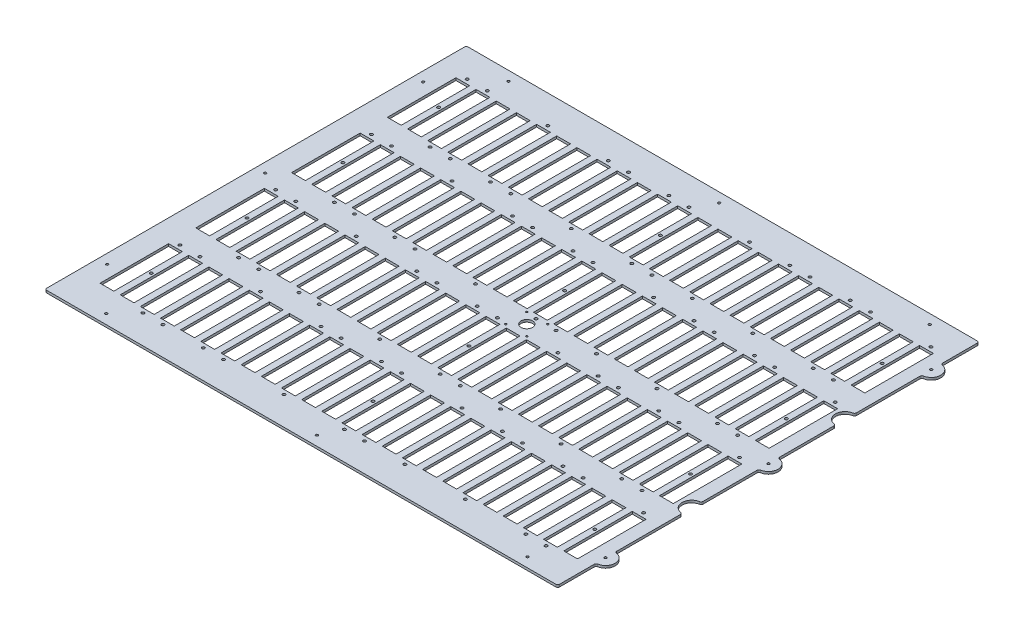
SolidWorks part; units mm, degrees
ref_plane "Front Plane" through (0, 0, 0) normal (0, 0, 1) x (1, 0, 0)
ref_plane "Top Plane" through (0, 0, 0) normal (0, 1, 0) x (1, 0, 0)
ref_plane "Right Plane" through (0, 0, 0) normal (1, 0, 0) x (0, 0, -1)
sketch "Sketch1" plane through (0, 0, 0) normal (0, 1, 0) x (1, 0, 0)
  line L0 (340.1822, 228.7524) -> (340.1822, 279.5524)
  line L1 (-340.1822, -279.5524) -> (340.1822, -279.5524)
  line L2 (-340.1822, -279.5524) -> (-340.1822, 279.5524)
  line L3 (-340.1822, 279.5524) -> (340.1822, 279.5524)
  line L4 (-340.1822, 0) -> (340.2584, 0) construction
  line L5 (-340.1822, -279.5524) -> (340.1822, 279.5524) construction
  line L6 (-340.1822, 279.5524) -> (340.1822, -279.5524) construction
  line L7 (340.1822, 114.4524) -> (340.1822, 203.3524)
  line L8 (340.1822, 12.6998) -> (340.1822, 89.0524)
  line L9 (340.1822, -279.5524) -> (340.1822, -228.7524)
  line L10 (340.1822, -89.0524) -> (340.1822, -12.6998)
  line L11 (340.1822, -203.3524) -> (340.1822, -114.4524)
  arc A0 (340.1822, 203.3524) -> (340.1822, 228.7524) centre (340.1822, 216.0524) ccw
  arc A1 (340.1822, -228.7524) -> (340.1822, -203.3524) centre (340.1822, -216.0524) ccw
  arc A2 (340.1822, -12.6998) -> (340.1822, 12.6998) centre (340.2584, 0) ccw
  arc A3 (340.1822, 114.4524) -> (340.1822, 89.0524) centre (340.1822, 101.7524) ccw
  arc A4 (340.1822, -89.0524) -> (340.1822, -114.4524) centre (340.1822, -101.7524) ccw
  point P0 (0, 0)
  dimension "D3" = 25.4
  dimension "D4" = 63.5
  dimension "D5" = 63.5
  dimension "D6" = 177.8
  dimension "D7" = 177.8
  dimension "D1" = 559.1048
  dimension "D2" = 680.3644
extrude "Boss-Extrude1" add sketch "Sketch1" along normal blind 3.175
sketch "Sketch17" plane through (0, 3.175, 0) normal (0, 1, 0) x (1, 0, 0)
  line L0 (340.1822, 279.5524) -> (-340.1822, 279.5524) construction
  line L1 (-314.7822, 254.1524) -> (327.4822, 254.1524) construction
  line L2 (-314.7822, 254.1524) -> (-314.7822, -254.1524) construction
  line L3 (-314.7822, -254.1524) -> (327.4822, -254.1524) construction
  line L4 (327.4822, 254.1524) -> (327.4822, -254.1524) construction
  line L5 (-340.1822, 279.5524) -> (-340.1822, -279.5524) construction
  line L6 (-340.1822, -279.5524) -> (340.1822, -279.5524) construction
  line L8 (-283.7677, 236.1184) -> (-265.4797, 236.1184)
  line L9 (-310.515, 236.1184) -> (-292.227, 236.1184)
  line L10 (-310.515, 236.1184) -> (-310.515, 145.1864)
  line L11 (-310.515, 145.1864) -> (-292.227, 145.1864)
  line L12 (-292.227, 236.1184) -> (-292.227, 145.1864)
  line L13 (-283.7677, 236.1184) -> (-283.7677, 145.1864)
  line L14 (-265.4797, 236.1184) -> (-265.4797, 145.1864)
  line L15 (-283.7677, 145.1864) -> (-265.4797, 145.1864)
  line L16 (-257.0204, 236.1184) -> (-238.7324, 236.1184)
  line L17 (-257.0204, 236.1184) -> (-257.0204, 145.1864)
  line L18 (-238.7324, 236.1184) -> (-238.7324, 145.1864)
  line L19 (-257.0204, 145.1864) -> (-238.7324, 145.1864)
  line L20 (-230.2731, 236.1184) -> (-211.9851, 236.1184)
  line L21 (-230.2731, 236.1184) -> (-230.2731, 145.1864)
  line L22 (-211.9851, 236.1184) -> (-211.9851, 145.1864)
  line L23 (-230.2731, 145.1864) -> (-211.9851, 145.1864)
  line L24 (-203.5258, 236.1184) -> (-185.2378, 236.1184)
  line L25 (-203.5258, 236.1184) -> (-203.5258, 145.1864)
  line L26 (-185.2378, 236.1184) -> (-185.2378, 145.1864)
  line L27 (-203.5258, 145.1864) -> (-185.2378, 145.1864)
  line L28 (-176.7785, 236.1184) -> (-158.4905, 236.1184)
  line L29 (-176.7785, 236.1184) -> (-176.7785, 145.1864)
  line L30 (-158.4905, 236.1184) -> (-158.4905, 145.1864)
  line L31 (-176.7785, 145.1864) -> (-158.4905, 145.1864)
  line L32 (-150.0312, 236.1184) -> (-131.7432, 236.1184)
  line L33 (-150.0312, 236.1184) -> (-150.0312, 145.1864)
  line L34 (-131.7432, 236.1184) -> (-131.7432, 145.1864)
  line L35 (-150.0312, 145.1864) -> (-131.7432, 145.1864)
  line L36 (-123.2839, 236.1184) -> (-104.9959, 236.1184)
  line L37 (-123.2839, 236.1184) -> (-123.2839, 145.1864)
  line L38 (-104.9959, 236.1184) -> (-104.9959, 145.1864)
  line L39 (-123.2839, 145.1864) -> (-104.9959, 145.1864)
  line L40 (-96.5366, 236.1184) -> (-78.2486, 236.1184)
  line L41 (-96.5366, 236.1184) -> (-96.5366, 145.1864)
  line L42 (-78.2486, 236.1184) -> (-78.2486, 145.1864)
  line L43 (-96.5366, 145.1864) -> (-78.2486, 145.1864)
  line L44 (-69.7893, 236.1184) -> (-51.5013, 236.1184)
  line L45 (-69.7893, 236.1184) -> (-69.7893, 145.1864)
  line L46 (-51.5013, 236.1184) -> (-51.5013, 145.1864)
  line L47 (-69.7893, 145.1864) -> (-51.5013, 145.1864)
  line L48 (-43.042, 236.1184) -> (-24.754, 236.1184)
  line L49 (-43.042, 236.1184) -> (-43.042, 145.1864)
  line L50 (-24.754, 236.1184) -> (-24.754, 145.1864)
  line L51 (-43.042, 145.1864) -> (-24.754, 145.1864)
  line L52 (-16.2947, 236.1184) -> (1.9933, 236.1184)
  line L53 (-16.2947, 236.1184) -> (-16.2947, 145.1864)
  line L54 (1.9933, 236.1184) -> (1.9933, 145.1864)
  line L55 (-16.2947, 145.1864) -> (1.9933, 145.1864)
  line L56 (10.4527, 236.1184) -> (28.7407, 236.1184)
  line L57 (10.4527, 236.1184) -> (10.4527, 145.1864)
  line L58 (28.7407, 236.1184) -> (28.7407, 145.1864)
  line L59 (10.4527, 145.1864) -> (28.7407, 145.1864)
  line L60 (37.2, 236.1184) -> (55.488, 236.1184)
  line L61 (37.2, 236.1184) -> (37.2, 145.1864)
  line L62 (55.488, 236.1184) -> (55.488, 145.1864)
  line L63 (37.2, 145.1864) -> (55.488, 145.1864)
  line L64 (63.9473, 236.1184) -> (82.2353, 236.1184)
  line L65 (63.9473, 236.1184) -> (63.9473, 145.1864)
  line L66 (82.2353, 236.1184) -> (82.2353, 145.1864)
  line L67 (63.9473, 145.1864) -> (82.2353, 145.1864)
  line L68 (90.6946, 236.1184) -> (108.9826, 236.1184)
  line L69 (90.6946, 236.1184) -> (90.6946, 145.1864)
  line L70 (108.9826, 236.1184) -> (108.9826, 145.1864)
  line L71 (90.6946, 145.1864) -> (108.9826, 145.1864)
  line L72 (117.4419, 236.1184) -> (135.7299, 236.1184)
  line L73 (117.4419, 236.1184) -> (117.4419, 145.1864)
  line L74 (135.7299, 236.1184) -> (135.7299, 145.1864)
  line L75 (117.4419, 145.1864) -> (135.7299, 145.1864)
  line L76 (144.1892, 236.1184) -> (162.4772, 236.1184)
  line L77 (144.1892, 236.1184) -> (144.1892, 145.1864)
  line L78 (162.4772, 236.1184) -> (162.4772, 145.1864)
  line L79 (144.1892, 145.1864) -> (162.4772, 145.1864)
  line L80 (170.9365, 236.1184) -> (189.2245, 236.1184)
  line L81 (170.9365, 236.1184) -> (170.9365, 145.1864)
  line L82 (189.2245, 236.1184) -> (189.2245, 145.1864)
  line L83 (170.9365, 145.1864) -> (189.2245, 145.1864)
  line L84 (197.6838, 236.1184) -> (215.9718, 236.1184)
  line L85 (197.6838, 236.1184) -> (197.6838, 145.1864)
  line L86 (215.9718, 236.1184) -> (215.9718, 145.1864)
  line L87 (197.6838, 145.1864) -> (215.9718, 145.1864)
  line L88 (224.4311, 236.1184) -> (242.7191, 236.1184)
  line L89 (224.4311, 236.1184) -> (224.4311, 145.1864)
  line L90 (242.7191, 236.1184) -> (242.7191, 145.1864)
  line L91 (224.4311, 145.1864) -> (242.7191, 145.1864)
  line L92 (251.1784, 236.1184) -> (269.4664, 236.1184)
  line L93 (251.1784, 236.1184) -> (251.1784, 145.1864)
  line L94 (269.4664, 236.1184) -> (269.4664, 145.1864)
  line L95 (251.1784, 145.1864) -> (269.4664, 145.1864)
  line L96 (277.9257, 236.1184) -> (296.2137, 236.1184)
  line L97 (277.9257, 236.1184) -> (277.9257, 145.1864)
  line L98 (296.2137, 236.1184) -> (296.2137, 145.1864)
  line L99 (277.9257, 145.1864) -> (296.2137, 145.1864)
  line L100 (304.673, 236.1184) -> (322.961, 236.1184)
  line L101 (304.673, 236.1184) -> (304.673, 145.1864)
  line L102 (322.961, 236.1184) -> (322.961, 145.1864)
  line L103 (304.673, 145.1864) -> (322.961, 145.1864)
  line L104 (-283.7677, 109.0422) -> (-265.4797, 109.0422)
  line L105 (-283.7677, 109.0422) -> (-283.7677, 18.1102)
  line L106 (-265.4797, 109.0422) -> (-265.4797, 18.1102)
  line L107 (-283.7677, 18.1102) -> (-265.4797, 18.1102)
  line L108 (-257.0204, 109.0422) -> (-238.7324, 109.0422)
  line L109 (-257.0204, 109.0422) -> (-257.0204, 18.1102)
  line L110 (-238.7324, 109.0422) -> (-238.7324, 18.1102)
  line L111 (-257.0204, 18.1102) -> (-238.7324, 18.1102)
  line L112 (-230.2731, 109.0422) -> (-211.9851, 109.0422)
  line L113 (-230.2731, 109.0422) -> (-230.2731, 18.1102)
  line L114 (-211.9851, 109.0422) -> (-211.9851, 18.1102)
  line L115 (-230.2731, 18.1102) -> (-211.9851, 18.1102)
  line L116 (-203.5258, 109.0422) -> (-185.2378, 109.0422)
  line L117 (-203.5258, 109.0422) -> (-203.5258, 18.1102)
  line L118 (-185.2378, 109.0422) -> (-185.2378, 18.1102)
  line L119 (-203.5258, 18.1102) -> (-185.2378, 18.1102)
  line L120 (-176.7785, 109.0422) -> (-158.4905, 109.0422)
  line L121 (-176.7785, 109.0422) -> (-176.7785, 18.1102)
  line L122 (-158.4905, 109.0422) -> (-158.4905, 18.1102)
  line L123 (-176.7785, 18.1102) -> (-158.4905, 18.1102)
  line L124 (-150.0312, 109.0422) -> (-131.7432, 109.0422)
  line L125 (-150.0312, 109.0422) -> (-150.0312, 18.1102)
  line L126 (-131.7432, 109.0422) -> (-131.7432, 18.1102)
  line L127 (-150.0312, 18.1102) -> (-131.7432, 18.1102)
  line L128 (-123.2839, 109.0422) -> (-104.9959, 109.0422)
  line L129 (-123.2839, 109.0422) -> (-123.2839, 18.1102)
  line L130 (-104.9959, 109.0422) -> (-104.9959, 18.1102)
  line L131 (-123.2839, 18.1102) -> (-104.9959, 18.1102)
  line L132 (-96.5366, 109.0422) -> (-78.2486, 109.0422)
  line L133 (-96.5366, 109.0422) -> (-96.5366, 18.1102)
  line L134 (-78.2486, 109.0422) -> (-78.2486, 18.1102)
  line L135 (-96.5366, 18.1102) -> (-78.2486, 18.1102)
  line L136 (-69.7893, 109.0422) -> (-51.5013, 109.0422)
  line L137 (-69.7893, 109.0422) -> (-69.7893, 18.1102)
  line L138 (-51.5013, 109.0422) -> (-51.5013, 18.1102)
  line L139 (-69.7893, 18.1102) -> (-51.5013, 18.1102)
  line L140 (-43.042, 109.0422) -> (-24.754, 109.0422)
  line L141 (-43.042, 109.0422) -> (-43.042, 18.1102)
  line L142 (-24.754, 109.0422) -> (-24.754, 18.1102)
  line L143 (-43.042, 18.1102) -> (-24.754, 18.1102)
  line L144 (-16.2947, 109.0422) -> (1.9933, 109.0422)
  line L145 (-16.2947, 109.0422) -> (-16.2947, 18.1102)
  line L146 (1.9933, 109.0422) -> (1.9933, 18.1102)
  line L147 (-16.2947, 18.1102) -> (1.9933, 18.1102)
  line L148 (10.4527, 109.0422) -> (28.7407, 109.0422)
  line L149 (10.4527, 109.0422) -> (10.4527, 18.1102)
  line L150 (28.7407, 109.0422) -> (28.7407, 18.1102)
  line L151 (10.4527, 18.1102) -> (28.7407, 18.1102)
  line L152 (37.2, 109.0422) -> (55.488, 109.0422)
  line L153 (37.2, 109.0422) -> (37.2, 18.1102)
  line L154 (55.488, 109.0422) -> (55.488, 18.1102)
  line L155 (37.2, 18.1102) -> (55.488, 18.1102)
  line L156 (63.9473, 109.0422) -> (82.2353, 109.0422)
  line L157 (63.9473, 109.0422) -> (63.9473, 18.1102)
  line L158 (82.2353, 109.0422) -> (82.2353, 18.1102)
  line L159 (63.9473, 18.1102) -> (82.2353, 18.1102)
  line L160 (90.6946, 109.0422) -> (108.9826, 109.0422)
  line L161 (90.6946, 109.0422) -> (90.6946, 18.1102)
  line L162 (108.9826, 109.0422) -> (108.9826, 18.1102)
  line L163 (90.6946, 18.1102) -> (108.9826, 18.1102)
  line L164 (117.4419, 109.0422) -> (135.7299, 109.0422)
  line L165 (117.4419, 109.0422) -> (117.4419, 18.1102)
  line L166 (135.7299, 109.0422) -> (135.7299, 18.1102)
  line L167 (117.4419, 18.1102) -> (135.7299, 18.1102)
  line L168 (144.1892, 109.0422) -> (162.4772, 109.0422)
  line L169 (144.1892, 109.0422) -> (144.1892, 18.1102)
  line L170 (162.4772, 109.0422) -> (162.4772, 18.1102)
  line L171 (144.1892, 18.1102) -> (162.4772, 18.1102)
  line L172 (170.9365, 109.0422) -> (189.2245, 109.0422)
  line L173 (170.9365, 109.0422) -> (170.9365, 18.1102)
  line L174 (189.2245, 109.0422) -> (189.2245, 18.1102)
  line L175 (170.9365, 18.1102) -> (189.2245, 18.1102)
  line L176 (197.6838, 109.0422) -> (215.9718, 109.0422)
  line L177 (197.6838, 109.0422) -> (197.6838, 18.1102)
  line L178 (215.9718, 109.0422) -> (215.9718, 18.1102)
  line L179 (197.6838, 18.1102) -> (215.9718, 18.1102)
  line L180 (224.4311, 109.0422) -> (242.7191, 109.0422)
  line L181 (224.4311, 109.0422) -> (224.4311, 18.1102)
  line L182 (242.7191, 109.0422) -> (242.7191, 18.1102)
  line L183 (224.4311, 18.1102) -> (242.7191, 18.1102)
  line L184 (251.1784, 109.0422) -> (269.4664, 109.0422)
  line L185 (251.1784, 109.0422) -> (251.1784, 18.1102)
  line L186 (269.4664, 109.0422) -> (269.4664, 18.1102)
  line L187 (251.1784, 18.1102) -> (269.4664, 18.1102)
  line L188 (277.9257, 109.0422) -> (296.2137, 109.0422)
  line L189 (277.9257, 109.0422) -> (277.9257, 18.1102)
  line L190 (296.2137, 109.0422) -> (296.2137, 18.1102)
  line L191 (277.9257, 18.1102) -> (296.2137, 18.1102)
  line L192 (304.673, 109.0422) -> (322.961, 109.0422)
  line L193 (304.673, 109.0422) -> (304.673, 18.1102)
  line L194 (322.961, 109.0422) -> (322.961, 18.1102)
  line L195 (304.673, 18.1102) -> (322.961, 18.1102)
  line L196 (-283.7677, -18.034) -> (-265.4797, -18.034)
  line L197 (-283.7677, -18.034) -> (-283.7677, -108.966)
  line L198 (-265.4797, -18.034) -> (-265.4797, -108.966)
  line L199 (-283.7677, -108.966) -> (-265.4797, -108.966)
  line L200 (-257.0204, -18.034) -> (-238.7324, -18.034)
  line L201 (-257.0204, -18.034) -> (-257.0204, -108.966)
  line L202 (-238.7324, -18.034) -> (-238.7324, -108.966)
  line L203 (-257.0204, -108.966) -> (-238.7324, -108.966)
  line L204 (-230.2731, -18.034) -> (-211.9851, -18.034)
  line L205 (-230.2731, -18.034) -> (-230.2731, -108.966)
  line L206 (-211.9851, -18.034) -> (-211.9851, -108.966)
  line L207 (-230.2731, -108.966) -> (-211.9851, -108.966)
  line L208 (-203.5258, -18.034) -> (-185.2378, -18.034)
  line L209 (-203.5258, -18.034) -> (-203.5258, -108.966)
  line L210 (-185.2378, -18.034) -> (-185.2378, -108.966)
  line L211 (-203.5258, -108.966) -> (-185.2378, -108.966)
  line L212 (-176.7785, -18.034) -> (-158.4905, -18.034)
  line L213 (-176.7785, -18.034) -> (-176.7785, -108.966)
  line L214 (-158.4905, -18.034) -> (-158.4905, -108.966)
  line L215 (-176.7785, -108.966) -> (-158.4905, -108.966)
  line L216 (-150.0312, -18.034) -> (-131.7432, -18.034)
  line L217 (-150.0312, -18.034) -> (-150.0312, -108.966)
  line L218 (-131.7432, -18.034) -> (-131.7432, -108.966)
  line L219 (-150.0312, -108.966) -> (-131.7432, -108.966)
  line L220 (-123.2839, -18.034) -> (-104.9959, -18.034)
  line L221 (-123.2839, -18.034) -> (-123.2839, -108.966)
  line L222 (-104.9959, -18.034) -> (-104.9959, -108.966)
  line L223 (-123.2839, -108.966) -> (-104.9959, -108.966)
  line L224 (-96.5366, -18.034) -> (-78.2486, -18.034)
  line L225 (-96.5366, -18.034) -> (-96.5366, -108.966)
  line L226 (-78.2486, -18.034) -> (-78.2486, -108.966)
  line L227 (-96.5366, -108.966) -> (-78.2486, -108.966)
  line L228 (-69.7893, -18.034) -> (-51.5013, -18.034)
  line L229 (-69.7893, -18.034) -> (-69.7893, -108.966)
  line L230 (-51.5013, -18.034) -> (-51.5013, -108.966)
  line L231 (-69.7893, -108.966) -> (-51.5013, -108.966)
  line L232 (-43.042, -18.034) -> (-24.754, -18.034)
  line L233 (-43.042, -18.034) -> (-43.042, -108.966)
  line L234 (-24.754, -18.034) -> (-24.754, -108.966)
  line L235 (-43.042, -108.966) -> (-24.754, -108.966)
  line L236 (-16.2947, -18.034) -> (1.9933, -18.034)
  line L237 (-16.2947, -18.034) -> (-16.2947, -108.966)
  line L238 (1.9933, -18.034) -> (1.9933, -108.966)
  line L239 (-16.2947, -108.966) -> (1.9933, -108.966)
  line L240 (10.4527, -18.034) -> (28.7407, -18.034)
  line L241 (10.4527, -18.034) -> (10.4527, -108.966)
  line L242 (28.7407, -18.034) -> (28.7407, -108.966)
  line L243 (10.4527, -108.966) -> (28.7407, -108.966)
  line L244 (37.2, -18.034) -> (55.488, -18.034)
  line L245 (37.2, -18.034) -> (37.2, -108.966)
  line L246 (55.488, -18.034) -> (55.488, -108.966)
  line L247 (37.2, -108.966) -> (55.488, -108.966)
  line L248 (63.9473, -18.034) -> (82.2353, -18.034)
  line L249 (63.9473, -18.034) -> (63.9473, -108.966)
  line L250 (82.2353, -18.034) -> (82.2353, -108.966)
  line L251 (63.9473, -108.966) -> (82.2353, -108.966)
  line L252 (90.6946, -18.034) -> (108.9826, -18.034)
  line L253 (90.6946, -18.034) -> (90.6946, -108.966)
  line L254 (108.9826, -18.034) -> (108.9826, -108.966)
  line L255 (90.6946, -108.966) -> (108.9826, -108.966)
  line L256 (117.4419, -18.034) -> (135.7299, -18.034)
  line L257 (117.4419, -18.034) -> (117.4419, -108.966)
  line L258 (135.7299, -18.034) -> (135.7299, -108.966)
  line L259 (117.4419, -108.966) -> (135.7299, -108.966)
  line L260 (144.1892, -18.034) -> (162.4772, -18.034)
  line L261 (144.1892, -18.034) -> (144.1892, -108.966)
  line L262 (162.4772, -18.034) -> (162.4772, -108.966)
  line L263 (144.1892, -108.966) -> (162.4772, -108.966)
  line L264 (170.9365, -18.034) -> (189.2245, -18.034)
  line L265 (170.9365, -18.034) -> (170.9365, -108.966)
  line L266 (189.2245, -18.034) -> (189.2245, -108.966)
  line L267 (170.9365, -108.966) -> (189.2245, -108.966)
  line L268 (197.6838, -18.034) -> (215.9718, -18.034)
  line L269 (197.6838, -18.034) -> (197.6838, -108.966)
  line L270 (215.9718, -18.034) -> (215.9718, -108.966)
  line L271 (197.6838, -108.966) -> (215.9718, -108.966)
  line L272 (224.4311, -18.034) -> (242.7191, -18.034)
  line L273 (224.4311, -18.034) -> (224.4311, -108.966)
  line L274 (242.7191, -18.034) -> (242.7191, -108.966)
  line L275 (224.4311, -108.966) -> (242.7191, -108.966)
  line L276 (251.1784, -18.034) -> (269.4664, -18.034)
  line L277 (251.1784, -18.034) -> (251.1784, -108.966)
  line L278 (269.4664, -18.034) -> (269.4664, -108.966)
  line L279 (251.1784, -108.966) -> (269.4664, -108.966)
  line L280 (277.9257, -18.034) -> (296.2137, -18.034)
  line L281 (277.9257, -18.034) -> (277.9257, -108.966)
  line L282 (296.2137, -18.034) -> (296.2137, -108.966)
  line L283 (277.9257, -108.966) -> (296.2137, -108.966)
  line L284 (304.673, -18.034) -> (322.961, -18.034)
  line L285 (304.673, -18.034) -> (304.673, -108.966)
  line L286 (322.961, -18.034) -> (322.961, -108.966)
  line L287 (304.673, -108.966) -> (322.961, -108.966)
  line L288 (-283.7677, -145.1102) -> (-265.4797, -145.1102)
  line L289 (-283.7677, -145.1102) -> (-283.7677, -236.0422)
  line L290 (-265.4797, -145.1102) -> (-265.4797, -236.0422)
  line L291 (-283.7677, -236.0422) -> (-265.4797, -236.0422)
  line L292 (-257.0204, -145.1102) -> (-238.7324, -145.1102)
  line L293 (-257.0204, -145.1102) -> (-257.0204, -236.0422)
  line L294 (-238.7324, -145.1102) -> (-238.7324, -236.0422)
  line L295 (-257.0204, -236.0422) -> (-238.7324, -236.0422)
  line L296 (-230.2731, -145.1102) -> (-211.9851, -145.1102)
  line L297 (-230.2731, -145.1102) -> (-230.2731, -236.0422)
  line L298 (-211.9851, -145.1102) -> (-211.9851, -236.0422)
  line L299 (-230.2731, -236.0422) -> (-211.9851, -236.0422)
  line L300 (-203.5258, -145.1102) -> (-185.2378, -145.1102)
  line L301 (-203.5258, -145.1102) -> (-203.5258, -236.0422)
  line L302 (-185.2378, -145.1102) -> (-185.2378, -236.0422)
  line L303 (-203.5258, -236.0422) -> (-185.2378, -236.0422)
  line L304 (-176.7785, -145.1102) -> (-158.4905, -145.1102)
  line L305 (-176.7785, -145.1102) -> (-176.7785, -236.0422)
  line L306 (-158.4905, -145.1102) -> (-158.4905, -236.0422)
  line L307 (-176.7785, -236.0422) -> (-158.4905, -236.0422)
  line L308 (-150.0312, -145.1102) -> (-131.7432, -145.1102)
  line L309 (-150.0312, -145.1102) -> (-150.0312, -236.0422)
  line L310 (-131.7432, -145.1102) -> (-131.7432, -236.0422)
  line L311 (-150.0312, -236.0422) -> (-131.7432, -236.0422)
  line L312 (-123.2839, -145.1102) -> (-104.9959, -145.1102)
  line L313 (-123.2839, -145.1102) -> (-123.2839, -236.0422)
  line L314 (-104.9959, -145.1102) -> (-104.9959, -236.0422)
  line L315 (-123.2839, -236.0422) -> (-104.9959, -236.0422)
  line L316 (-96.5366, -145.1102) -> (-78.2486, -145.1102)
  line L317 (-96.5366, -145.1102) -> (-96.5366, -236.0422)
  line L318 (-78.2486, -145.1102) -> (-78.2486, -236.0422)
  line L319 (-96.5366, -236.0422) -> (-78.2486, -236.0422)
  line L320 (-69.7893, -145.1102) -> (-51.5013, -145.1102)
  line L321 (-69.7893, -145.1102) -> (-69.7893, -236.0422)
  line L322 (-51.5013, -145.1102) -> (-51.5013, -236.0422)
  line L323 (-69.7893, -236.0422) -> (-51.5013, -236.0422)
  line L324 (-43.042, -145.1102) -> (-24.754, -145.1102)
  line L325 (-43.042, -145.1102) -> (-43.042, -236.0422)
  line L326 (-24.754, -145.1102) -> (-24.754, -236.0422)
  line L327 (-43.042, -236.0422) -> (-24.754, -236.0422)
  line L328 (-16.2947, -145.1102) -> (1.9933, -145.1102)
  line L329 (-16.2947, -145.1102) -> (-16.2947, -236.0422)
  line L330 (1.9933, -145.1102) -> (1.9933, -236.0422)
  line L331 (-16.2947, -236.0422) -> (1.9933, -236.0422)
  line L332 (10.4527, -145.1102) -> (28.7407, -145.1102)
  line L333 (10.4527, -145.1102) -> (10.4527, -236.0422)
  line L334 (28.7407, -145.1102) -> (28.7407, -236.0422)
  line L335 (10.4527, -236.0422) -> (28.7407, -236.0422)
  line L336 (37.2, -145.1102) -> (55.488, -145.1102)
  line L337 (37.2, -145.1102) -> (37.2, -236.0422)
  line L338 (55.488, -145.1102) -> (55.488, -236.0422)
  line L339 (37.2, -236.0422) -> (55.488, -236.0422)
  line L340 (63.9473, -145.1102) -> (82.2353, -145.1102)
  line L341 (63.9473, -145.1102) -> (63.9473, -236.0422)
  line L342 (82.2353, -145.1102) -> (82.2353, -236.0422)
  line L343 (63.9473, -236.0422) -> (82.2353, -236.0422)
  line L344 (90.6946, -145.1102) -> (108.9826, -145.1102)
  line L345 (90.6946, -145.1102) -> (90.6946, -236.0422)
  line L346 (108.9826, -145.1102) -> (108.9826, -236.0422)
  line L347 (90.6946, -236.0422) -> (108.9826, -236.0422)
  line L348 (117.4419, -145.1102) -> (135.7299, -145.1102)
  line L349 (117.4419, -145.1102) -> (117.4419, -236.0422)
  line L350 (135.7299, -145.1102) -> (135.7299, -236.0422)
  line L351 (117.4419, -236.0422) -> (135.7299, -236.0422)
  line L352 (144.1892, -145.1102) -> (162.4772, -145.1102)
  line L353 (144.1892, -145.1102) -> (144.1892, -236.0422)
  line L354 (162.4772, -145.1102) -> (162.4772, -236.0422)
  line L355 (144.1892, -236.0422) -> (162.4772, -236.0422)
  line L356 (170.9365, -145.1102) -> (189.2245, -145.1102)
  line L357 (170.9365, -145.1102) -> (170.9365, -236.0422)
  line L358 (189.2245, -145.1102) -> (189.2245, -236.0422)
  line L359 (170.9365, -236.0422) -> (189.2245, -236.0422)
  line L360 (197.6838, -145.1102) -> (215.9718, -145.1102)
  line L361 (197.6838, -145.1102) -> (197.6838, -236.0422)
  line L362 (215.9718, -145.1102) -> (215.9718, -236.0422)
  line L363 (197.6838, -236.0422) -> (215.9718, -236.0422)
  line L364 (224.4311, -145.1102) -> (242.7191, -145.1102)
  line L365 (224.4311, -145.1102) -> (224.4311, -236.0422)
  line L366 (242.7191, -145.1102) -> (242.7191, -236.0422)
  line L367 (224.4311, -236.0422) -> (242.7191, -236.0422)
  line L368 (251.1784, -145.1102) -> (269.4664, -145.1102)
  line L369 (251.1784, -145.1102) -> (251.1784, -236.0422)
  line L370 (269.4664, -145.1102) -> (269.4664, -236.0422)
  line L371 (251.1784, -236.0422) -> (269.4664, -236.0422)
  line L372 (277.9257, -145.1102) -> (296.2137, -145.1102)
  line L373 (277.9257, -145.1102) -> (277.9257, -236.0422)
  line L374 (296.2137, -145.1102) -> (296.2137, -236.0422)
  line L375 (277.9257, -236.0422) -> (296.2137, -236.0422)
  line L376 (304.673, -145.1102) -> (322.961, -145.1102)
  line L377 (304.673, -145.1102) -> (304.673, -236.0422)
  line L378 (322.961, -145.1102) -> (322.961, -236.0422)
  line L379 (304.673, -236.0422) -> (322.961, -236.0422)
  line L380 (-310.515, 109.0422) -> (-292.227, 109.0422)
  line L381 (-310.515, 109.0422) -> (-310.515, 18.1102)
  line L382 (-292.227, 109.0422) -> (-292.227, 18.1102)
  line L383 (-310.515, 18.1102) -> (-292.227, 18.1102)
  line L384 (-310.515, -18.034) -> (-292.227, -18.034)
  line L385 (-310.515, -18.034) -> (-310.515, -108.966)
  line L386 (-292.227, -18.034) -> (-292.227, -108.966)
  line L387 (-310.515, -108.966) -> (-292.227, -108.966)
  line L388 (-310.515, -145.1102) -> (-292.227, -145.1102)
  line L389 (-310.515, -145.1102) -> (-310.515, -236.0422)
  line L390 (-292.227, -145.1102) -> (-292.227, -236.0422)
  line L391 (-310.515, -236.0422) -> (-292.227, -236.0422)
  line L392 (340.2584, -279.5524) -> (340.2584, -228.6) construction
  line L393 (340.1822, -203.3524) -> (340.1822, -114.4524) construction
  dimension "D1" = 25.4
  dimension "D2" = 25.4
  dimension "D3" = 25.4
  dimension "D4" = 12.7
  dimension "D5" = 18.288
  dimension "D6" = 90.932
  dimension "D7" = 4.2672
  dimension "D8" = 18.034
  dimension "D9" = 508.3048
  dimension "D10" = 642.2644
  dimension "D11" = 24
  dimension "D13" = 17.2974
  dimension "D14" = 43.5102
  dimension "D12" = 4
extrude "Cut-Extrude5" cut sketch "Sketch17" against normal through all
hole_wizard "#25 (0.1495) Diameter Hole1" positions "Sketch18" profile "Sketch19" hole size "#25" standard "ANSI Inch" end condition through all
sketch "Sketch18" plane through (0, 3.175, 0) normal (0, 1, 0) x (1, 0, 0)
  line L10 (-340.1822, 241.9604) -> (340.1822, 241.9604) construction
  line L11 (-340.1822, 279.5524) -> (-340.1822, -279.5524) construction
  line L12 (340.1822, 228.7524) -> (340.1822, 279.5524) construction
  line L16 (-340.1822, 139.3444) -> (340.2584, 139.3444) construction
  line L17 (340.2584, 12.7) -> (340.2584, 95.25) construction
  line L23 (-301.4472, 139.3444) -> (-301.4472, 241.9604) construction
  line L24 (-274.6966, 139.3444) -> (-274.6966, 241.9604) construction
  line L25 (-247.946, 139.3444) -> (-247.946, 241.9604) construction
  line L26 (-221.1954, 139.3444) -> (-221.1954, 241.9604) construction
  line L27 (-194.4448, 139.3444) -> (-194.4448, 241.9604) construction
  line L28 (-167.6941, 139.3444) -> (-167.6941, 241.9604) construction
  line L29 (-140.9435, 139.3444) -> (-140.9435, 241.9604) construction
  line L30 (-114.1929, 139.3444) -> (-114.1929, 241.9604) construction
  line L31 (-87.4423, 139.3444) -> (-87.4423, 241.9604) construction
  line L32 (-60.6917, 139.3444) -> (-60.6917, 241.9604) construction
  line L33 (-33.941, 139.3444) -> (-33.941, 241.9604) construction
  line L34 (-7.1904, 139.3444) -> (-7.1904, 241.9604) construction
  line L35 (19.5602, 139.3444) -> (19.5602, 241.9604) construction
  line L36 (46.3108, 139.3444) -> (46.3108, 241.9604) construction
  line L37 (73.0614, 139.3444) -> (73.0614, 241.9604) construction
  line L38 (99.812, 139.3444) -> (99.812, 241.9604) construction
  line L39 (126.5627, 139.3444) -> (126.5627, 241.9604) construction
  line L40 (153.3133, 139.3444) -> (153.3133, 241.9604) construction
  line L41 (180.0639, 139.3444) -> (180.0639, 241.9604) construction
  line L42 (206.8145, 139.3444) -> (206.8145, 241.9604) construction
  line L43 (233.5651, 139.3444) -> (233.5651, 241.9604) construction
  line L44 (260.3158, 139.3444) -> (260.3158, 241.9604) construction
  line L45 (287.0664, 139.3444) -> (287.0664, 241.9604) construction
  line L46 (313.817, 139.3444) -> (313.817, 241.9604) construction
  line L48 (322.961, -108.966) -> (322.961, -18.034) construction
  line L49 (322.961, -18.034) -> (304.673, -18.034) construction
  point P259 (-301.4472, 241.9604)
  point P269 (-274.6966, 241.9604)
  point P270 (-247.946, 139.3444)
  point P272 (-221.1954, 139.3444)
  point P275 (-194.4448, 241.9604)
  point P276 (-167.6941, 139.3444)
  point P278 (-140.9435, 139.3444)
  point P281 (-114.1929, 241.9604)
  point P283 (-87.4423, 241.9604)
  point P284 (-60.6917, 139.3444)
  point P287 (-33.941, 241.9604)
  point P289 (-7.1904, 241.9604)
  point P290 (19.5602, 139.3444)
  point P292 (46.3108, 139.3444)
  point P295 (73.0614, 241.9604)
  point P296 (99.812, 139.3444)
  point P299 (126.5627, 241.9604)
  point P301 (153.3133, 241.9604)
  point P302 (180.0639, 139.3444)
  point P305 (206.8145, 241.9604)
  point P307 (233.5651, 241.9604)
  point P308 (260.3158, 139.3444)
  point P310 (287.0664, 139.3444)
  point P313 (313.817, 241.9604)
  point P365 (-301.4472, 114.8842)
  point P366 (-274.6966, 114.8842)
  point P367 (-247.946, 12.2682)
  point P368 (-221.1954, 12.2682)
  point P369 (-194.4448, 114.8842)
  point P370 (-167.6941, 12.2682)
  point P371 (-140.9435, 12.2682)
  point P372 (-114.1929, 114.8842)
  point P373 (-87.4423, 114.8842)
  point P374 (-60.6917, 12.2682)
  point P375 (-33.941, 114.8842)
  point P376 (-7.1904, 114.8842)
  point P377 (19.5602, 12.2682)
  point P378 (46.3108, 12.2682)
  point P379 (73.0614, 114.8842)
  point P380 (99.812, 12.2682)
  point P381 (126.5627, 114.8842)
  point P382 (153.3133, 114.8842)
  point P383 (180.0639, 12.2682)
  point P384 (206.8145, 114.8842)
  point P385 (233.5651, 114.8842)
  point P386 (260.3158, 12.2682)
  point P387 (287.0664, 12.2682)
  point P388 (313.817, 114.8842)
  point P389 (-301.4472, -12.192)
  point P390 (-274.6966, -12.192)
  point P391 (-247.946, -114.808)
  point P392 (-221.1954, -114.808)
  point P393 (-194.4448, -12.192)
  point P394 (-167.6941, -114.808)
  point P395 (-140.9435, -114.808)
  point P396 (-114.1929, -12.192)
  point P397 (-87.4423, -12.192)
  point P398 (-60.6917, -114.808)
  point P399 (-33.941, -12.192)
  point P400 (-7.1904, -12.192)
  point P401 (19.5602, -114.808)
  point P402 (46.3108, -114.808)
  point P403 (73.0614, -12.192)
  point P404 (99.812, -114.808)
  point P405 (126.5627, -12.192)
  point P406 (153.3133, -12.192)
  point P407 (180.0639, -114.808)
  point P408 (206.8145, -12.192)
  point P409 (233.5651, -12.192)
  point P410 (260.3158, -114.808)
  point P411 (287.0664, -114.808)
  point P412 (313.817, -12.192)
  point P413 (-301.4472, -139.2682)
  point P414 (-274.6966, -139.2682)
  point P415 (-247.946, -241.8842)
  point P416 (-221.1954, -241.8842)
  point P417 (-194.4448, -139.2682)
  point P418 (-167.6941, -241.8842)
  point P419 (-140.9435, -241.8842)
  point P420 (-114.1929, -139.2682)
  point P421 (-87.4423, -139.2682)
  point P422 (-60.6917, -241.8842)
  point P423 (-33.941, -139.2682)
  point P424 (-7.1904, -139.2682)
  point P425 (19.5602, -241.8842)
  point P426 (46.3108, -241.8842)
  point P427 (73.0614, -139.2682)
  point P428 (99.812, -241.8842)
  point P429 (126.5627, -139.2682)
  point P430 (153.3133, -139.2682)
  point P431 (180.0639, -241.8842)
  point P432 (206.8145, -139.2682)
  point P433 (233.5651, -139.2682)
  point P434 (260.3158, -241.8842)
  point P435 (287.0664, -241.8842)
  point P436 (313.817, -139.2682)
  dimension "D1" = 9.144
  dimension "D2" = 35.8946
  dimension "D3" = 5.842
  dimension "D4" = 30.3022
  dimension "D5" = 132.9182
sketch "Sketch19" plane through (313.817, 3.175, 139.2682) normal (1, 0, 0) x (0, 0, 1)
  line L0 (0, 0) -> (0, 3.175)
  line L1 (0, 3.175) -> (1.8986, 3.175)
  line L2 (1.8986, 3.175) -> (1.8986, 0)
  line L5 (1.8986, 0) -> (0, 0)
  line L11 (0, -6.35) -> (0, 107.95) construction
  dimension "Thru Hole Dia." = 3.7973
  dimension "Thru Hole Depth" = 3.175
fillet "Fillet1" radius 2.54 14 edges at (-340.1822, 1.5875, -279.5524) (-340.1822, 1.5875, 279.5524) (340.1822, 1.5875, -279.5524) (340.1822, 1.5875, -228.7524) (340.1822, 1.5875, 279.5524) (340.1822, 1.5875, 228.7524) (340.1822, 1.5875, 203.3524) (340.1822, 1.5875, 114.4524) (340.1822, 1.5875, 89.0524) (340.1822, 1.5875, 12.6998) (340.1822, 1.5875, -12.6998) (340.1822, 1.5875, -89.0524) (340.1822, 1.5875, -114.4524) (340.1822, 1.5875, -203.3524)
hole_wizard "#6 Clearance Hole1" positions "Sketch8" profile "Sketch9" hole size "#6" standard "ANSI Inch" end condition through all
sketch "Sketch8" plane through (0, 3.175, 0) normal (0, 1, 0) x (1, 0, 0)
  line L13 (-292.227, 236.1184) -> (-283.7677, 145.1864) construction
  line L15 (1.9933, 236.1184) -> (10.4527, 145.1864) construction
  line L17 (296.2137, 236.1184) -> (304.673, 145.1864) construction
  line L18 (-292.227, 109.0422) -> (-283.7677, 18.1102) construction
  line L19 (1.9933, 109.0422) -> (10.4527, 18.1102) construction
  line L20 (296.2137, 109.0422) -> (304.673, 18.1102) construction
  line L21 (-292.227, -18.034) -> (-283.7677, -108.966) construction
  line L22 (1.9933, -18.034) -> (10.4527, -108.966) construction
  line L23 (296.2137, -18.034) -> (304.673, -108.966) construction
  line L24 (-292.227, -145.1102) -> (-283.7677, -236.0422) construction
  line L25 (1.9933, -145.1102) -> (10.4527, -236.0422) construction
  line L26 (296.2137, -145.1102) -> (304.673, -236.0422) construction
  point P129 (-287.9973, 190.6524)
  point P131 (6.223, 190.6524)
  point P133 (300.4433, 190.6524)
  point P146 (-287.9973, 63.5762)
  point P147 (6.223, 63.5762)
  point P148 (300.4433, 63.5762)
  point P155 (-287.9973, -63.5)
  point P156 (6.223, -63.5)
  point P157 (300.4433, -63.5)
  point P164 (-287.9973, -190.5762)
  point P165 (6.223, -190.5762)
  point P166 (300.4433, -190.5762)
  dimension "D1" = 4
sketch "Sketch9" plane through (300.4433, 3.175, 190.5762) normal (1, 0, 0) x (0, 0, 1)
  line L0 (0, 0) -> (0, 3.175)
  line L1 (0, 3.175) -> (1.8986, 3.175)
  line L2 (1.8986, 3.175) -> (1.8986, 0)
  line L5 (1.8986, 0) -> (0, 0)
  line L11 (0, -6.35) -> (0, 107.95) construction
  dimension "Thru Hole Dia." = 3.7973
  dimension "Thru Hole Depth" = 3.175
hole_wizard "#2 Clearance Hole1" positions "Sketch13" profile "Sketch14" hole size "#2" standard "ANSI Inch" end condition through all
sketch "Sketch13" plane through (0, 3.175, 0) normal (0, 1, 0) x (1, 0, 0)
  line L9 (322.961, -108.966) -> (322.961, -18.034) construction
  line L10 (322.961, -18.034) -> (304.673, -18.034) construction
  line L18 (10.4527, 18.1102) -> (28.7407, -18.034) construction
  line L21 (5.6261, -13.9319) -> (33.5661, -13.9319) construction
  line L22 (5.6261, -13.9319) -> (5.6261, 14.0081) construction
  line L23 (5.6261, 14.0081) -> (33.5661, 14.0081) construction
  line L24 (33.5661, -13.9319) -> (33.5661, 14.0081) construction
  line L25 (5.6261, -13.9319) -> (33.5661, 14.0081) construction
  line L26 (5.6261, 14.0081) -> (33.5661, -13.9319) construction
  line L27 (10.4527, 18.1102) -> (28.7407, 18.1102) construction
  point P129 (5.6261, 14.0081)
  point P132 (5.6261, -13.9319)
  point P135 (33.5661, -13.9319)
  point P138 (33.5661, 14.0081)
  dimension "D1" = 27.94
  dimension "D2" = 27.94
  dimension "D3" = 4.1021
sketch "Sketch14" plane through (33.5661, 3.175, -14.0081) normal (1, 0, 0) x (0, 0, 1)
  line L0 (0, 0) -> (0, 3.175)
  line L1 (0, 3.175) -> (1.2192, 3.175)
  line L2 (1.2192, 3.175) -> (1.2192, 0)
  line L5 (1.2192, 0) -> (0, 0)
  line L11 (0, -6.35) -> (0, 107.95) construction
  dimension "Thru Hole Dia." = 2.4384
  dimension "Thru Hole Depth" = 3.175
sketch "Sketch20" plane through (0, 3.175, 0) normal (0, 1, 0) x (1, 0, 0)
  line L0 (5.6261, 14.0081) -> (33.5661, -13.9319) construction
  circle A0 centre (19.5961, 0.0381) radius 7.62
  dimension "D1" = 15.24
extrude "Cut-Extrude6" cut sketch "Sketch20" against normal through all
hole_wizard "1/8 (0.125) Diameter Hole1" positions "Sketch21" profile "Sketch22" hole size "1/8" standard "ANSI Inch" end condition through all
sketch "Sketch21" plane through (0, 3.175, 0) normal (0, 1, 0) x (1, 0, 0)
  point P0 (287.3502, 266.8524)
  point P12 (287.3502, -266.8524)
  point P15 (7.9502, -266.8524)
  point P18 (-271.4498, -266.8524)
  point P21 (-327.4822, -209.55)
  point P24 (-327.4822, 0)
  point P27 (-327.4822, 209.55)
  point P30 (-271.4498, 266.8524)
  point P33 (7.9502, 266.8524)
  point P48 (340.1822, 216.0524)
  point P51 (340.2584, 0)
  point P54 (340.1822, -216.0524)
sketch "Sketch22" plane through (287.3502, 3.175, -266.8524) normal (1, 0, 0) x (0, 0, 1)
  line L0 (0, 0) -> (0, 3.175)
  line L1 (0, 3.175) -> (1.5875, 3.175)
  line L2 (1.5875, 3.175) -> (1.5875, 0)
  line L5 (1.5875, 0) -> (0, 0)
  line L11 (0, -6.35) -> (0, 107.95) construction
  dimension "Thru Hole Dia." = 3.175
  dimension "Thru Hole Depth" = 3.175
